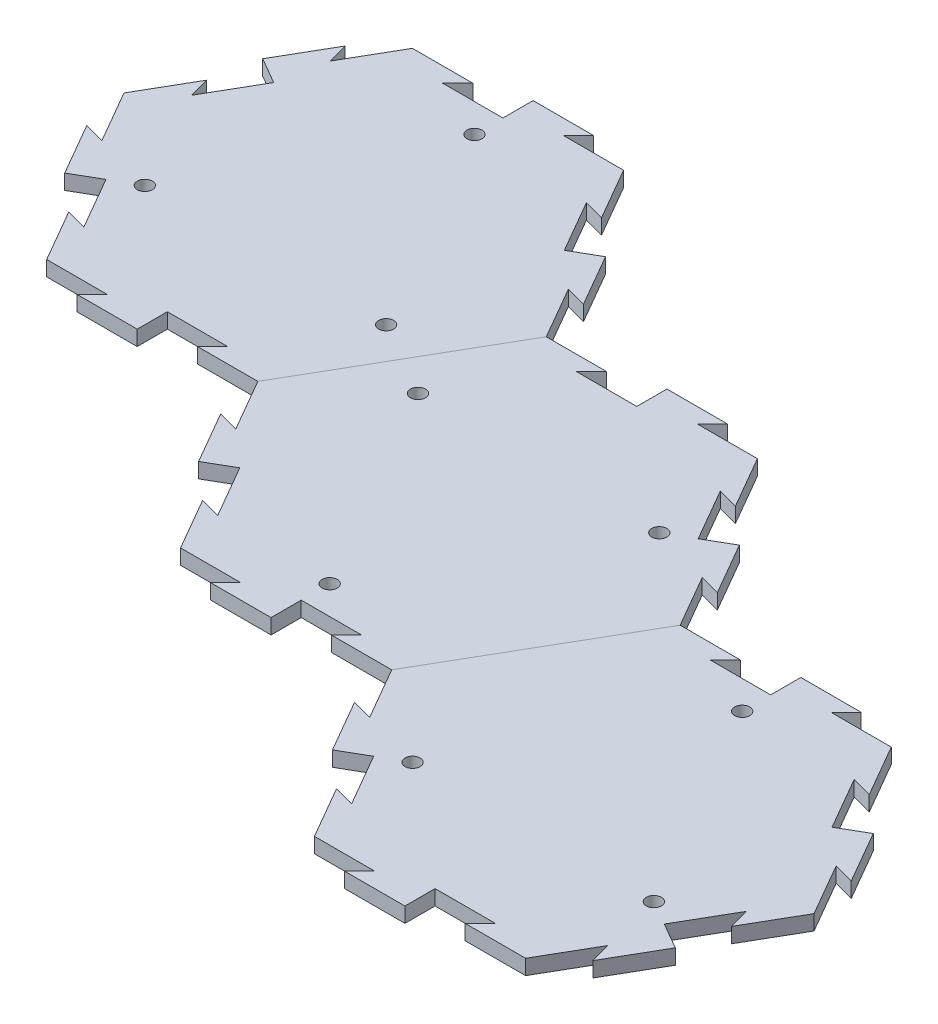
SolidWorks part; units mm, degrees
material "Cedar"
ref_plane "Front Plane" through (0, 0, 0) normal (0, 0, 1) x (1, 0, 0)
ref_plane "Top Plane" through (0, 0, 0) normal (0, 1, 0) x (1, 0, 0)
ref_plane "Right Plane" through (0, 0, 0) normal (1, 0, 0) x (0, 0, -1)
sketch "Sketch1" plane through (0, 0, 0) normal (0, 1, 0) x (1, 0, 0)
  line L0 (0, 0) -> (88.9, 0) construction
  line L1 (88.9, 0) -> (44.45, 76.9897)
  line L2 (44.45, 76.9897) -> (-44.45, 76.9897)
  line L3 (-44.45, 76.9897) -> (-88.9, 0)
  line L4 (-88.9, 0) -> (-44.45, -76.9897)
  line L5 (-44.45, -76.9897) -> (44.45, -76.9897)
  line L6 (44.45, -76.9897) -> (88.9, 0)
  circle A0 centre (0, 0) radius 76.9897 construction
  dimension "D1" = 88.9
extrude "Boss-Extrude1" add sketch "Sketch1" against normal blind 6.35
sketch "Sketch2" plane through (0, 0, 0) normal (0, 1, 0) x (1, 0, 0)
  point P1 (0, 0)
ref_axis "Axis1" through (0, 0, 0) along (0, 1, 0)
sketch "Sketch9" plane through (0, 0, 0) normal (0, 1, 0) x (1, 0, 0)
  line L1 (50.8, -29.3294) -> (0, 58.6588) construction
  line L2 (0, 58.6588) -> (-50.8, -29.3294) construction
  line L3 (-50.8, -29.3294) -> (50.8, -29.3294) construction
  circle A0 centre (0, 0) radius 29.3294 construction
  circle A1 centre (-50.8, -29.3294) radius 3.175
  dimension "D2" = 6.35
  dimension "D1" = 101.6
extrude "Cut-Extrude3" cut sketch "Sketch9" against normal through all
pattern_circular "CirPattern6" count 3 over 360 about axis through (0, 0, 0) along (0, 1, 0) of "Cut-Extrude3"
mirror "Mirror3" about plane through (44.45, -6.35, 76.9897) normal (0.866, 0, 0.5) of bodies 121 125
sketch "Sketch10" plane through (0, 0, 0) normal (0, 1, 0) x (1, 0, 0)
  line L0 (44.45, 76.9897) -> (57.15, 54.9926) construction
  line L1 (57.15, 54.9926) -> (48.4757, 57.3169)
  line L2 (48.4757, 57.3169) -> (61.1757, 35.3198)
  line L3 (61.1757, 35.3198) -> (66.675, 38.4948)
  line L4 (57.15, 54.9926) -> (66.675, 38.4948)
  line L5 (88.9, 0) -> (44.45, 76.9897) construction
  dimension "D1" = 45
  dimension "D2" = 6.35
extrude "Cut-Extrude4" cut sketch "Sketch10" against normal through all
sketch "Sketch11" plane through (0, 0, 0) normal (0, 1, 0) x (1, 0, 0)
  line L0 (66.675, 38.4948) -> (88.9, 0) construction
  line L1 (66.675, 38.4948) -> (72.1743, 41.6698)
  line L2 (72.1743, 41.6698) -> (84.8743, 19.6728)
  line L3 (84.8743, 19.6728) -> (76.2, 21.997)
  line L4 (76.2, 21.997) -> (66.675, 38.4948)
  line L5 (76.2, 21.997) -> (88.9, 0) construction
  line L6 (76.2, 21.997) -> (88.9, 0) construction
  line L7 (88.9, 0) -> (66.675, 38.4948) construction
  line L8 (44.45, -76.9897) -> (88.9, 0) construction
  dimension "D1" = 45
  dimension "D2" = 6.35
extrude "Boss-Extrude4" add sketch "Sketch11" against normal blind 6.35
pattern_circular "CirPattern7" count 6 over 360 about axis through (0, 0, 0) along (0, 1, 0) skipping 5 of "Cut-Extrude4", "Boss-Extrude4"
mirror "Mirror4" about plane through (222.25, -6.35, 76.9897) normal (0.866, 0, 0.5) of bodies 126 129
sketch "Sketch12" plane through (0, 0, 0) normal (0, 1, 0) x (1, 0, 0)
  line L0 (177.8, 0) -> (88.9, -153.9793) construction
  point P4 (133.35, -76.9897)
ref_axis "Axis2" through (133.35, 0, 76.9897) along (0, 1, 0)
sketch "Sketch13" plane through (0, 0, 0) normal (0, 1, 0) x (1, 0, 0)
  line L0 (177.8, 0) -> (190.5, -21.997) construction
  line L1 (190.5, -21.997) -> (181.8257, -19.6728)
  line L2 (181.8257, -19.6728) -> (194.5257, -41.6698)
  line L3 (194.5257, -41.6698) -> (200.025, -38.4948)
  line L4 (190.5, -21.997) -> (200.025, -38.4948)
  line L5 (177.8, 0) -> (222.25, -76.9897) construction
  dimension "D1" = 45
  dimension "D2" = 6.35
extrude "Cut-Extrude5" cut sketch "Sketch13" against normal through all
sketch "Sketch14" plane through (0, 0, 0) normal (0, 1, 0) x (1, 0, 0)
  line L0 (200.025, -38.4948) -> (222.25, -76.9897) construction
  line L1 (200.025, -38.4948) -> (205.5243, -35.3198)
  line L2 (205.5243, -35.3198) -> (218.2243, -57.3169)
  line L3 (218.2243, -57.3169) -> (209.55, -54.9926)
  line L4 (209.55, -54.9926) -> (200.025, -38.4948)
  line L5 (209.55, -54.9926) -> (222.25, -76.9897) construction
  line L6 (209.55, -54.9926) -> (222.25, -76.9897) construction
  dimension "D1" = 45
  dimension "D2" = 6.35
extrude "Boss-Extrude5" add sketch "Sketch14" against normal blind 6.35
pattern_circular "CirPattern8" count 6 over 360 about axis through (133.35, 0, 76.9897) along (0, 1, 0) skipping 2, 5 of "Cut-Extrude5", "Boss-Extrude5"
sketch "Sketch15" plane through (0, 0, 0) normal (0, 1, 0) x (1, 0, 0)
  line L0 (311.15, -76.9897) -> (222.25, -230.969) construction
  point P4 (266.7, -153.9793)
ref_axis "Axis3" through (266.7, 0, 153.9793) along (0, 1, 0)
sketch "Sketch16" plane through (0, 0, 0) normal (0, 1, 0) x (1, 0, 0)
  line L0 (311.15, -76.9897) -> (323.85, -98.9867) construction
  line L1 (323.85, -98.9867) -> (315.1757, -96.6624)
  line L2 (315.1757, -96.6624) -> (327.8757, -118.6595)
  line L3 (327.8757, -118.6595) -> (333.375, -115.4845)
  line L4 (323.85, -98.9867) -> (333.375, -115.4845)
  line L5 (355.6, -153.9793) -> (311.15, -76.9897) construction
  point P5 (311.15, -76.9897)
  point P7 (333.375, -115.4845)
  dimension "D1" = 45
  dimension "D2" = 6.35
extrude "Cut-Extrude6" cut sketch "Sketch16" against normal through all
sketch "Sketch17" plane through (0, 0, 0) normal (0, 1, 0) x (1, 0, 0)
  line L0 (333.375, -115.4845) -> (355.6, -153.9793) construction
  line L1 (333.375, -115.4845) -> (338.8743, -112.3095)
  line L2 (338.8743, -112.3095) -> (351.5743, -134.3065)
  line L3 (351.5743, -134.3065) -> (342.9, -131.9823)
  line L4 (342.9, -131.9823) -> (333.375, -115.4845)
  line L5 (342.9, -131.9823) -> (355.6, -153.9793) construction
  line L6 (342.9, -131.9823) -> (355.6, -153.9793) construction
  line L7 (355.6, -153.9793) -> (333.375, -115.4845) construction
  point P5 (355.6, -153.9793)
  point P7 (333.375, -115.4845)
  point P9 (342.2926, -130.9302)
  dimension "D1" = 6.35
  dimension "D2" = 45
extrude "Boss-Extrude6" add sketch "Sketch17" against normal up to surface (6.35 mm away) up to face at (320.2496, -6.35, 181.7212)
pattern_circular "CirPattern9" count 6 over 360 about axis through (266.7, 0, 153.9793) along (0, 1, 0) skipping 2 of "Cut-Extrude6", "Boss-Extrude6"
